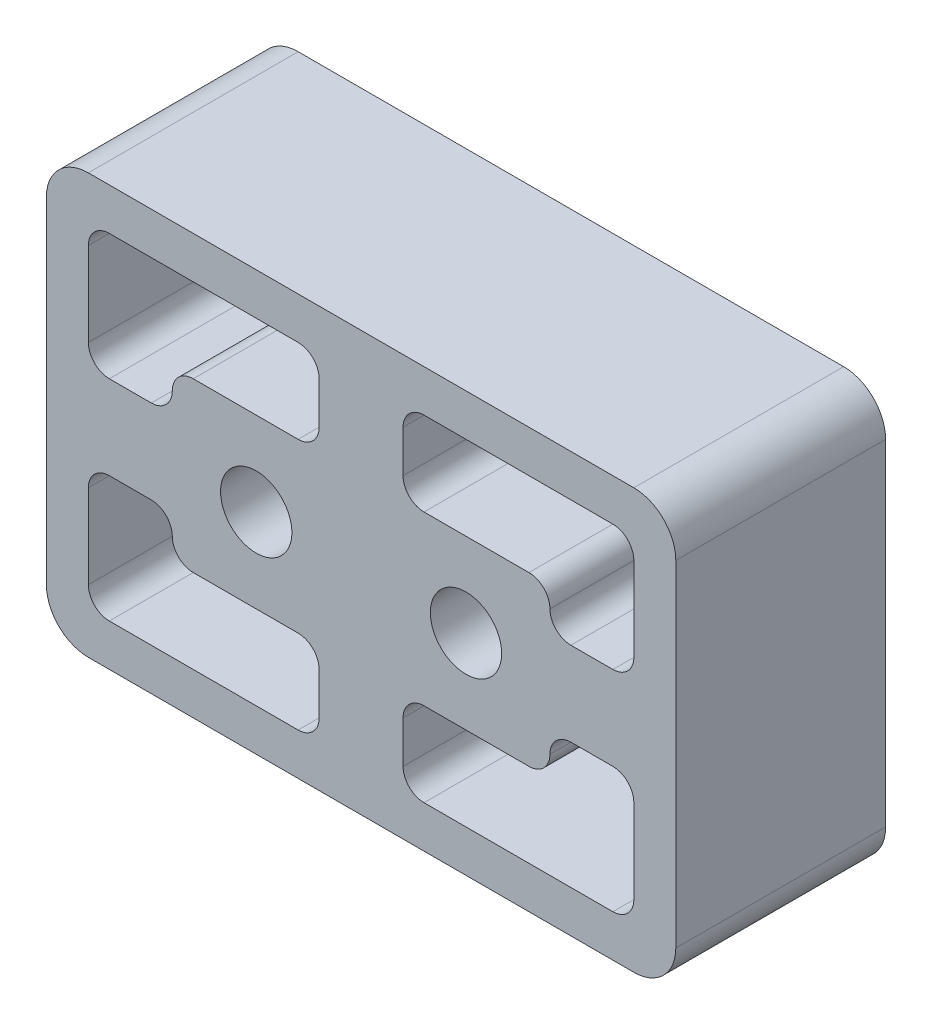
SolidWorks part; units mm, degrees
ref_plane "前视基准面" through (0, 0, 0) normal (0, 0, 1) x (1, 0, 0)
ref_plane "上视基准面" through (0, 0, 0) normal (0, 1, 0) x (1, 0, 0)
ref_plane "右视基准面" through (0, 0, 0) normal (1, 0, 0) x (0, 0, -1)
sketch "草图1" plane through (0, 0, 0) normal (0, 0, 1) x (1, 0, 0)
  line L1 (-15, -10) -> (15, -10)
  line L2 (-15, -10) -> (-15, 10)
  line L3 (-15, 10) -> (15, 10)
  line L4 (15, -10) -> (15, 10)
  line L5 (-15, -10) -> (15, 10) construction
  line L6 (-15, 10) -> (15, -10) construction
  point P0 (0, 0)
  dimension "D1" = 20
  dimension "D2" = 30
extrude "凸台-拉伸1" add sketch "草图1" along normal blind 10
fillet "圆角1" radius 2 4 edges at (-15, -10, 5) (15, -10, 5) (15, 10, 5) (-15, 10, 5)
sketch "草图2" plane through (0, 0, 10) normal (0, 0, 1) x (1, 0, 0)
  line L0 (0, 0) -> (50000, 0) construction
  line L1 (0, 0) -> (0, 50000) construction
  circle A0 centre (5, 0) radius 1.7
  circle A1 centre (-5, 0) radius 1.7
  dimension "D1" = 3.4
  dimension "D2" = 10
extrude "切除-拉伸1" cut sketch "草图2" against normal through all
sketch "草图3" plane through (0, 0, 10) normal (0, 0, 1) x (1, 0, 0)
  line L0 (-13, 2) -> (-13, 8)
  line L3 (9, 2) -> (13, 2)
  line L4 (0, 0) -> (50000, 0) construction
  line L5 (0, 0) -> (0, 50000) construction
  line L6 (-13, 8) -> (-2, 8)
  line L9 (-2, 8) -> (-2, 4)
  line L12 (9, 4) -> (9, 2)
  line L13 (-2, 4) -> (-9, 4)
  line L16 (-9, 4) -> (-9, 2)
  line L17 (-9, 2) -> (-13, 2)
  line L18 (-15, 8) -> (-15, -8) construction
  line L19 (13, 10) -> (-13, 10) construction
  line L20 (2, 4) -> (9, 4)
  line L21 (2, 8) -> (2, 4)
  line L22 (13, 8) -> (2, 8)
  line L23 (13, 2) -> (13, 8)
  line L24 (13, -2) -> (13, -8)
  line L25 (13, -8) -> (2, -8)
  line L26 (2, -8) -> (2, -4)
  line L27 (2, -4) -> (9, -4)
  line L28 (-9, -2) -> (-13, -2)
  line L29 (-9, -4) -> (-9, -2)
  line L30 (-2, -4) -> (-9, -4)
  line L31 (9, -4) -> (9, -2)
  line L32 (-2, -8) -> (-2, -4)
  line L33 (-13, -8) -> (-2, -8)
  line L34 (9, -2) -> (13, -2)
  line L35 (-13, -2) -> (-13, -8)
  dimension "D3" = 4
  dimension "D1" = 2
  dimension "D2" = 2
  dimension "D5" = 2
  dimension "D6" = 2
extrude "切除-拉伸2" cut sketch "草图3" against normal through all
fillet "圆角2" radius 1 24 edges at (-2, -4, 5) (2, 8, 5) (13, 8, 5) (13, 2, 5) (2, 4, 5) (9, 2, 5) (9, 4, 5) (13, -2, 5) (2, -8, 5) (2, -4, 5) (9, -2, 5) (9, -4, 5) (13, -8, 5) (-2, -8, 5) (-13, -8, 5) (-13, -2, 5) (-9, -2, 5) (-9, -4, 5) (-2, 8, 5) (-2, 4, 5) (-9, 4, 5) (-9, 2, 5) (-13, 2, 5) (-13, 8, 5)
equation "\"4。3\"=4.3483"
